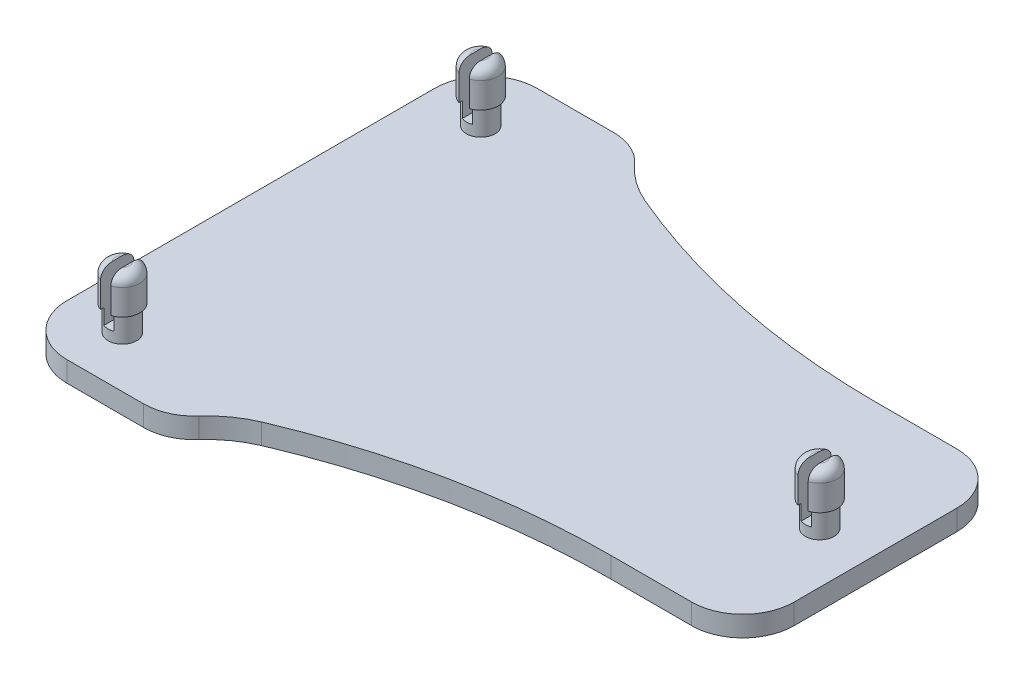
SolidWorks part; units mm, degrees
ref_plane "Front Plane" through (0, 0, 0) normal (0, 0, 1) x (1, 0, 0)
ref_plane "Top Plane" through (0, 0, 0) normal (0, 1, 0) x (1, 0, 0)
ref_plane "Right Plane" through (0, 0, 0) normal (1, 0, 0) x (0, 0, -1)
sketch "Sketch1" plane through (0, 0, 0) normal (0, 1, 0) x (1, 0, 0)
  line L0 (-30.5, -22.95) -> (-30.5, 22.95)
  line L1 (28.5, -20.95) -> (-28.5, -20.95) construction
  line L2 (28.5, -20.95) -> (28.5, 20.95) construction
  line L3 (28.5, 20.95) -> (-28.5, 20.95) construction
  line L4 (-28.5, -20.95) -> (-28.5, 20.95) construction
  line L5 (28.5, -20.95) -> (-28.5, 20.95) construction
  line L6 (28.5, 20.95) -> (-28.5, -20.95) construction
  line L7 (-15.5, 22.95) -> (-30.5, 22.95)
  line L8 (30.5, -12.95) -> (30.5, 12.95)
  line L9 (-15.5, -22.95) -> (-30.5, -22.95)
  line L10 (0, 0) -> (-42.2176, 0) construction
  line L11 (-15.5, 22.95) -> (-15.5, 11.3939) construction
  line L12 (30.5, 12.95) -> (17.6169, 12.95) construction
  line L13 (17.6169, 12.95) -> (-11.7527, 12.95) construction
  line L14 (-15.5, 22.95) -> (-15.5, 20.95)
  line L15 (17.6169, 12.95) -> (30.5, 12.95)
  line L16 (17.6169, -12.95) -> (30.5, -12.95)
  line L17 (-15.5, -22.95) -> (-15.5, -20.95)
  line L18 (30.5, 22.95) -> (-30.5, 22.95) construction
  line L19 (30.5, -22.95) -> (30.5, 22.95) construction
  line L20 (30.5, -22.95) -> (-30.5, -22.95) construction
  circle A2 centre (25.5, -0.45) radius 1.6
  arc A3 (-15.5, 20.95) -> (17.6169, 12.95) centre (17.6169, 85.4958) ccw
  arc A4 (-15.5, -20.95) -> (17.6169, -12.95) centre (17.6169, -85.4958) cw
  point P0 (0, 0)
  dimension "D7" = 3
  dimension "D8" = 20.5
  dimension "D1" = 41.9
  dimension "D2" = 57
  dimension "D9" = 15
  dimension "D10" = 10
  dimension "D3" = 2
extrude "Boss-Extrude1" add sketch "Sketch1" along normal blind 2
fillet "Fillet1" radius 10 2 edges at (-15.5, 1, 20.95) (-15.5, 1, -20.95)
fillet "Fillet2" radius 5 6 edges at (-30.5, 1, -22.95) (-30.5, 1, 22.95) (-15.5, 1, 22.95) (-15.5, 1, -22.95) (30.5, 1, -12.95) (30.5, 1, 12.95)
ref_plane "Plane1" through (-15.5, 0, 0) normal (-1, 0, 0) x (0, 0, 1)
sketch "Sketch2" plane through (0, 0, 0) normal (0, 0, 1) x (1, 0, 0)
  line L0 (-15.5, 3.9252) -> (-15.5, 0.5) construction
  line L1 (-30.5, 0) -> (-30.5, 2) construction
  line L2 (-18.0286, 0) -> (-14.2938, 0) construction
  line L3 (-18.5, -2.5) -> (-18.5, 0)
  line L4 (-25.5, 0) -> (-18.0286, 0) construction
  line L5 (-12.5, -2.5) -> (-12.513, 0)
  line L6 (-14.2938, 0) -> (-10.7321, 0) construction
  line L7 (-15.5, -1) -> (-15.5, -2.714) construction
  line L8 (-18.5, 0) -> (-12.513, 0)
  circle A0 centre (-15.5, -2.5) radius 1.5
  arc A1 (-18.5, -2.5) -> (-12.5002, -2.4689) centre (-15.5, -2.5) ccw
  circle A2 centre (-15.5, -2.5) radius 3 construction
  dimension "D2" = 2.5
  dimension "D3" = 1.5
  dimension "D1" = 15
extrude "Boss-Extrude2" add sketch "Sketch2" along normal mid plane 20 contours L3 A1 L5 L8 A0 region at (-18.4186, -1.25, 0)
sketch "Sketch3" plane through (-18.5, 0, 0) normal (-1, 0, 0) x (0, 0, 1)
  line L0 (10, 0) -> (-10, 0) construction
  line L1 (-2.5, 0) -> (2.5, 0)
  line L2 (-2.5, 0) -> (-2.5, -5.5)
  line L3 (-2.5, -5.5) -> (2.5, -5.5)
  line L4 (2.5, 0) -> (2.5, -5.5)
  line L5 (-10, -5.5) -> (10, -5.5) construction
  line L6 (10, -2.5) -> (10, 0) construction
  line L9 (-10, -2.5) -> (-10, 0) construction
  point P10 (0, 0)
  dimension "D1" = 10
  dimension "D3" = 20
extrude "Cut-Extrude1" cut sketch "Sketch3" against normal blind 20
sketch "Sketch5" plane through (0, 2, 0) normal (0, 1, 0) x (1, 0, 0)
  circle A0 centre (-25.1, 17.05) radius 1.4
  circle A1 centre (-25.1, -17.95) radius 1.4
  circle A2 centre (25.5, -0.45) radius 1.4
extrude "Boss-Extrude6" add sketch "Sketch5" along normal blind 6
sketch "Sketch6" plane through (0, 8, 0) normal (0, 1, 0) x (1, 0, 0)
  circle A0 centre (-25.1, 17.05) radius 1.7
  circle A1 centre (25.5, -0.45) radius 1.7
  circle A2 centre (-25.1, -17.95) radius 1.7
extrude "Boss-Extrude7" add sketch "Sketch6" against normal blind 3.5
fillet "Fillet4" radius 1 2 edges at (-25.1, 8, 19.65) (-25.1, 8, -15.35)
fillet "Fillet5" radius 1 1 edges at (25.5, 8, 2.15)
sketch "Sketch7" plane through (0, 8, 0) normal (0, 1, 0) x (1, 0, 0)
  line L1 (-24.6, 19.7752) -> (-25.6, 19.7752)
  line L2 (-24.6, 19.7752) -> (-24.6, 14.3248)
  line L3 (-24.6, 14.3248) -> (-25.6, 14.3248)
  line L4 (-25.6, 19.7752) -> (-25.6, 14.3248)
  line L5 (-24.6, 19.7752) -> (-25.6, 14.3248) construction
  line L6 (-24.6, 14.3248) -> (-25.6, 19.7752) construction
  line L7 (-24.6, -15.6084) -> (-25.6, -15.6084)
  line L8 (-24.6, -15.6084) -> (-24.6, -20.2916)
  line L9 (-24.6, -20.2916) -> (-25.6, -20.2916)
  line L10 (-25.6, -15.6084) -> (-25.6, -20.2916)
  line L11 (-24.6, -15.6084) -> (-25.6, -20.2916) construction
  line L12 (-24.6, -20.2916) -> (-25.6, -15.6084) construction
  line L13 (26, 2.4829) -> (25, 2.4829)
  line L14 (26, 2.4829) -> (26, -3.3829)
  line L15 (26, -3.3829) -> (25, -3.3829)
  line L16 (25, 2.4829) -> (25, -3.3829)
  line L17 (26, 2.4829) -> (25, -3.3829) construction
  line L18 (26, -3.3829) -> (25, 2.4829) construction
  point P0 (-25.1, 17.05)
  point P6 (-25.1, -17.95)
  point P12 (25.5, -0.45)
extrude "Cut-Extrude3" cut sketch "Sketch7" against normal blind 5
sketch "Sketch8" plane through (0, 0, 0) normal (0, -1, 0) x (1, 0, 0)
  circle A0 centre (25.5, 0.45) radius 1.6
extrude "Boss-Extrude8" add sketch "Sketch8" against normal blind 2
